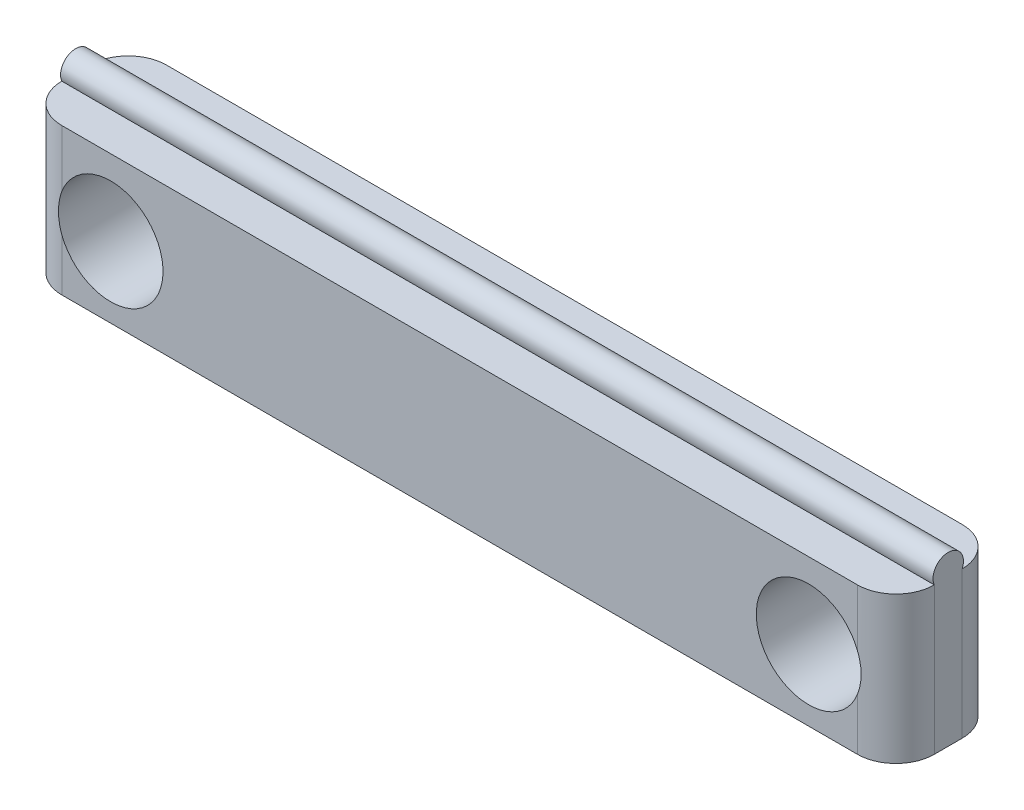
SolidWorks part; units mm, degrees
ref_plane "Front Plane" through (0, 0, 0) normal (0, 0, 1) x (1, 0, 0)
ref_plane "Top Plane" through (0, 0, 0) normal (0, 1, 0) x (1, 0, 0)
ref_plane "Right Plane" through (0, 0, 0) normal (1, 0, 0) x (0, 0, -1)
sketch "Sketch1" plane through (0, 0, 0) normal (0, 0, 1) x (1, 0, 0)
  line L0 (0, 0) -> (1000, 0) construction
  line L6 (-125, 108.7005) -> (1125, 108.7005)
  line L7 (-125, 108.7005) -> (-125, -101.5569)
  line L8 (-125, -101.5569) -> (1125, -101.5569)
  line L9 (1125, 108.7005) -> (1125, -101.5569)
  dimension "D1" = 210.2574
  dimension "D2" = 1250
extrude "Boss-Extrude1" add sketch "Sketch1" along normal blind 150
sketch "Sketch2" plane through (0, 0, 150) normal (0, 0, 1) x (1, 0, 0)
  line L0 (1000, 0) -> (0, 0) construction
  circle A0 centre (0, 0) radius 75
  circle A1 centre (1000, 0) radius 75
  dimension "D1" = 150
  dimension "D3" = 1000
  dimension "D2" = 2
extrude "Cut-Extrude1" cut sketch "Sketch2" against normal blind 150
fillet "Fillet3" radius 55 4 edges at (1125, 3.5718, 0) (1125, 3.5718, 150) (-125, 3.5718, 150) (-125, 3.5718, 0)
sketch "Sketch3" plane through (-125, 0, 0) normal (-1, 0, 0) x (0, 0, 1)
  line L0 (95, 108.7005) -> (55, 108.7005) construction
  line L1 (95, 108.7005) -> (55, 108.7005)
  arc A0 (55, 108.7005) -> (95, 108.7005) centre (75, 117.3517) cw
extrude "Boss-Extrude2" add sketch "Sketch3" against normal through all
